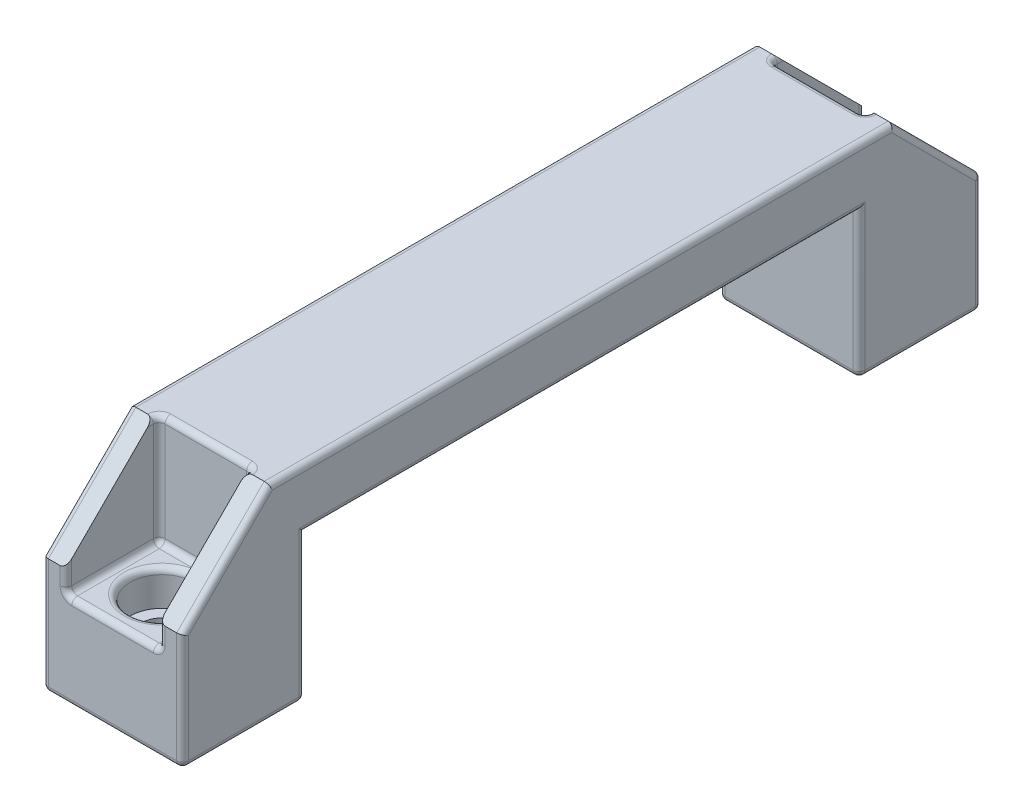
SolidWorks part; units mm, degrees
ref_plane "前视基准面" through (0, 0, 0) normal (0, 0, 1) x (1, 0, 0)
ref_plane "上视基准面" through (0, 0, 0) normal (0, 1, 0) x (1, 0, 0)
ref_plane "右视基准面" through (0, 0, 0) normal (1, 0, 0) x (0, 0, -1)
sketch "草图1" plane through (0, 0, 0) normal (1, 0, 0) x (0, 0, -1)
  line L0 (0, 0) -> (0, 50000) construction
  line L1 (-53.5, 0) -> (53.5, 0)
  line L2 (53.5, 0) -> (68.5, -15)
  line L3 (68.5, -15) -> (68.5, -35)
  line L4 (68.5, -35) -> (47.5, -35)
  line L5 (47.5, -35) -> (47.5, -10)
  line L6 (47.5, -10) -> (-47.5, -10)
  line L7 (-47.5, -35) -> (-47.5, -10)
  line L8 (-68.5, -35) -> (-47.5, -35)
  line L9 (-68.5, -15) -> (-68.5, -35)
  line L10 (-53.5, 0) -> (-68.5, -15)
  point P11 (0, -10)
  point P15 (0, 0)
  dimension "D1" = 137
  dimension "D2" = 95
  dimension "D3" = 20
  dimension "D4" = 135
  dimension "D5" = 25
  dimension "D6" = 10
extrude "凸台-拉伸1" add sketch "草图1" along normal mid plane 24
ref_plane "基准面1" through (0, -19, 0) normal (0, -1, 0) x (-1, 0, 0)
sketch "草图2" plane through (0, -19, 0) normal (0, -1, 0) x (-1, 0, 0)
  line L0 (-12, -68.5) -> (12, -68.5) construction
  line L1 (8, -68.5) -> (-8, -68.5)
  line L2 (8, -68.5) -> (8, -52.5)
  line L3 (8, -52.5) -> (-8, -52.5)
  line L4 (-8, -68.5) -> (-8, -52.5)
  line L5 (0, 0) -> (0, -50000) construction
  line L6 (0, 0) -> (50000, 0) construction
  line L7 (-8, 68.5) -> (-8, 52.5)
  line L8 (8, 52.5) -> (-8, 52.5)
  line L9 (8, 68.5) -> (8, 52.5)
  line L10 (8, 68.5) -> (-8, 68.5)
  dimension "D1" = 16
  dimension "D2" = 16
extrude "切除-拉伸1" cut sketch "草图2" against normal blind 24
hole_wizard "打孔尺寸根据六角头螺栓 C 级的类型3" positions "草图4" profile "草图5" counterbore size "M6" standard "Gb" end condition through all
sketch "草图4" plane through (0, -19, 0) normal (0, 1, 0) x (1, 0, 0)
  line L1 (0, 0) -> (0, 50000) construction
  line L2 (8, -68.5) -> (-8, -68.5) construction
  line L3 (-8, 68.5) -> (8, 68.5) construction
  point P7 (0, -60)
  point P9 (0, 60)
  dimension "D1" = 8.5
  dimension "D2" = 8.5
sketch "草图5" plane through (0, -19, 60) normal (1, 0, 0) x (0, 0, 1)
  line L0 (0, 0) -> (0, 16)
  line L1 (0, 16) -> (3.5, 16)
  line L3 (3.5, 16) -> (3.5, 6)
  line L4 (3.5, 6) -> (5.5, 6)
  line L5 (5.5, 6) -> (5.5, 0)
  line L7 (5.5, 0) -> (0, 0)
  line L11 (0, -6.35) -> (0, 107.95) construction
  dimension "通孔孔直径" = 7
  dimension "通孔孔深度" = 16
  dimension "柱形沉头孔直径" = 11
  dimension "柱形沉头孔深度" = 6
fillet "圆角1" radius 1 52 edges at (-8, 0, 53) (8, 0, 53) (8, -17, 68.5) (-8, -17, 68.5) (8, 0, -53) (-8, 0, -53) (0, -35, -47.5) (0, -35, -56.5) (0, -35, 68.5) (0, -35, 47.5) (0, -35, 63.5) (0, 0, 52.5) (8, -9.5, 52.5) (-8, -9.5, 52.5) (0, -19, 52.5) (8, -19, 60.5) (0, -19, 68.5) (-8, -19, 60.5) (0, -19, 65.5) (8, -19, -60.5) (-8, -19, -60.5) (0, -19, -54.5) (0, 0, -52.5) (-8, -9.5, -52.5) (0, -19, -52.5) (8, -9.5, -52.5) (0, -35, -68.5) (10, -15, -68.5) (8, -17, -68.5) (0, -19, -68.5) (-8, -17, -68.5) (-10, -15, -68.5) (-12, 0, 0) (-12, -7.5, 61) (-12, -25, 68.5) (-12, -35, 58) (-12, -22.5, 47.5) (-12, -10, 0) (-12, -22.5, -47.5) (-12, -35, -58) (-12, -25, -68.5) (-12, -7.5, -61) (12, -25, -68.5) (12, -35, -58) (12, -22.5, -47.5) (12, -10, 0) (12, -22.5, 47.5) (12, -35, 58) (12, -25, 68.5) (12, -7.5, 61) (12, 0, 0) (12, -7.5, -61)
